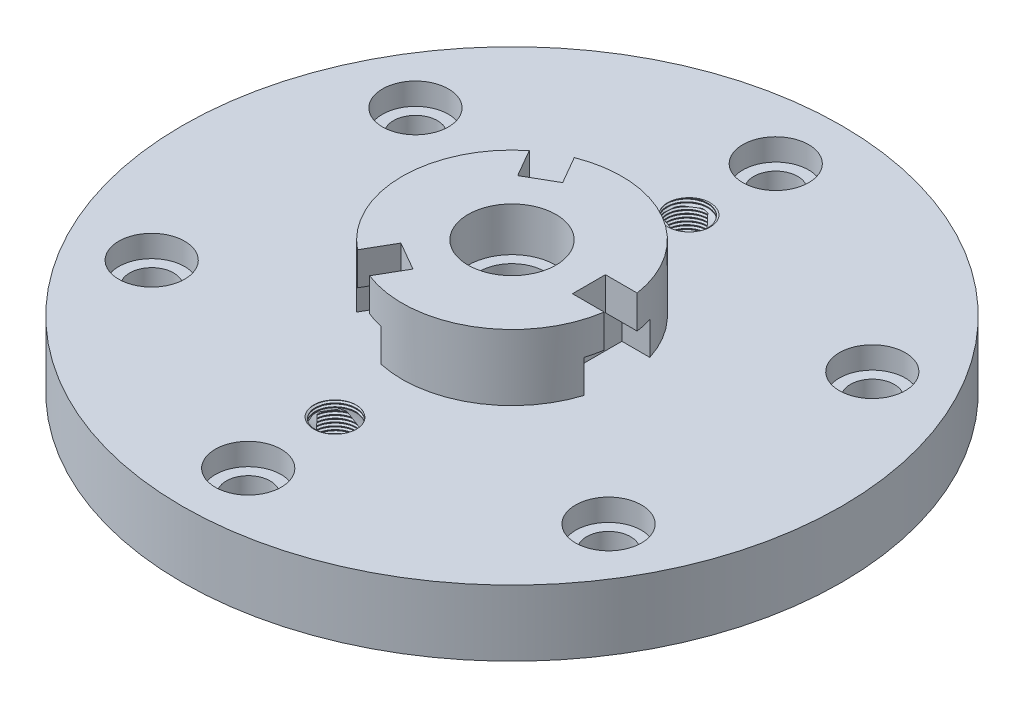
SolidWorks part; units mm, degrees
ref_plane "Front Plane" through (0, 0, 0) normal (0, 0, 1) x (1, 0, 0)
ref_plane "Top Plane" through (0, 0, 0) normal (0, 1, 0) x (1, 0, 0)
ref_plane "Right Plane" through (0, 0, 0) normal (1, 0, 0) x (0, 0, -1)
ref_axis "Z" through (0, 55, 0) along (0, -1, 0)
ref_axis "Y" through (0, 0, 165) along (0, 0, -1)
ref_axis "X" through (165, 0, 0) along (-1, 0, 0)
sketch "Sketch2" plane through (0, 0, 0) normal (0, 0, 1) x (1, 0, 0)
  line L0 (0, -58.6304) -> (0, 71.3696)
  line L1 (0, 55) -> (0, -55) construction
  line L2 (0, 71.3696) -> (-50, 71.3696)
  line L3 (-50, 71.3696) -> (-50, 41.3696)
  line L4 (-50, 41.3696) -> (-150, 41.3696)
  line L5 (-150, 41.3696) -> (-150, 11.3696)
  line L6 (-150, 11.3696) -> (-65, 11.3696)
  line L7 (-60, 6.3696) -> (-60, -3.6304)
  line L8 (-55, -8.6304) -> (-40, -8.6304)
  line L9 (-30, -18.6304) -> (-30, -58.6304)
  line L10 (-30, -58.6304) -> (0, -58.6304)
  arc A0 (-60, -3.6304) -> (-55, -8.6304) centre (-55, -3.6304) ccw
  arc A1 (-65, 11.3696) -> (-60, 6.3696) centre (-65, 6.3696) cw
  arc A2 (-40, -8.6304) -> (-30, -18.6304) centre (-40, -18.6304) cw
  point P15 (-60, -8.6304)
  point P18 (-60, 11.3696)
  point P21 (-30, -8.6304)
  dimension "D9" = 5
  dimension "D10" = 10
  dimension "D1" = 50
  dimension "D2" = 100
  dimension "D3" = 30
  dimension "D4" = 20
  dimension "D5" = 50
  dimension "D6" = 60
  dimension "D7" = 30
  dimension "D8" = 30
revolve "Revolve1" add sketch "Sketch2" angle 360 about axis through (0, 55, 0) along (0, -1, 0)
sketch "Sketch3" plane through (0, 0, 0) normal (0, 0, 1) x (1, 0, 0)
  line L0 (0, 71.3696) -> (-20, 71.3696)
  line L1 (50, 71.3696) -> (-50, 71.3696) construction
  line L2 (-20, 71.3696) -> (-20, 51.3696)
  line L4 (-20, 51.3696) -> (-15, 51.3696)
  line L5 (-15, 51.3696) -> (-15, -58.6304)
  line L6 (-30, -58.6304) -> (30, -58.6304) construction
  line L7 (-15, -58.6304) -> (0, -58.6304)
  line L8 (0, -58.6304) -> (0, 71.3696)
  dimension "D1" = 20
  dimension "D2" = 20
  dimension "D3" = 5
  dimension "D4" = 110
revolve "Cut-Revolve1" cut sketch "Sketch3" angle 360 about L8
sketch "Sketch6" plane through (0, 71.3696, 0) normal (0, 1, 0) x (1, 0, 0)
  line L0 (-11.0048, -34.0609) -> (-23.9952, -26.5609)
  line L1 (35, 7.5) -> (61.5171, 7.5)
  line L2 (35, 7.5) -> (35, -7.5)
  line L3 (35, -7.5) -> (61.5171, -7.5)
  line L4 (61.5171, 7.5) -> (61.5171, -7.5)
  line L5 (-11.0048, -34.0609) -> (-24.2634, -57.0254)
  line L6 (-24.2634, -57.0254) -> (-37.2537, -49.5254)
  line L7 (-23.9952, -26.5609) -> (-37.2537, -49.5254)
  line L8 (-23.9952, 26.5609) -> (-11.0048, 34.0609)
  line L9 (-23.9952, 26.5609) -> (-37.2537, 49.5254)
  line L10 (-37.2537, 49.5254) -> (-24.2634, 57.0254)
  line L11 (-11.0048, 34.0609) -> (-24.2634, 57.0254)
  point P16 (0, 0)
  dimension "D1" = 15
  dimension "D2" = 7.5
  dimension "D3" = 35
extrude "Cut-Extrude2" cut sketch "Sketch6" against normal blind 30
sketch "Sketch8" plane through (0, 41.3696, 0) normal (0, 1, 0) x (1, 0, 0)
  line L0 (-4.5096, -37.8109) -> (-30.4904, -22.8109)
  line L1 (35, 15) -> (65.7776, 15)
  line L2 (35, 15) -> (35, -15)
  line L3 (35, -15) -> (65.7776, -15)
  line L4 (65.7776, 15) -> (65.7776, -15)
  line L5 (-4.5096, -37.8109) -> (-19.8984, -64.4651)
  line L6 (-19.8984, -64.4651) -> (-45.8792, -49.4651)
  line L7 (-30.4904, -22.8109) -> (-45.8792, -49.4651)
  line L8 (-30.4904, 22.8109) -> (-4.5096, 37.8109)
  line L9 (-30.4904, 22.8109) -> (-45.8792, 49.4651)
  line L10 (-45.8792, 49.4651) -> (-19.8984, 64.4651)
  line L11 (-4.5096, 37.8109) -> (-19.8984, 64.4651)
  point P16 (0, 0)
  dimension "D1" = 30
  dimension "D2" = 35
  dimension "D3" = 15
extrude "Cut-Extrude3" cut sketch "Sketch8" along normal blind 15
sketch "Sketch9" plane through (0, 41.3696, 0) normal (0, 1, 0) x (1, 0, 0)
  circle A0 centre (0, 0) radius 120
  point P3 (0, 120)
  point P4 (0, -80)
  dimension "D1" = 240
  dimension "D2" = 80
hole_wizard "CBORE for M10 Hex Head Bolt1" positions "3DSketch1" profile "Sketch10" counterbore size "M10" standard "ANSI Metric" end condition through all
sketch3d "3DSketch1"
  point P0 (0, 41.3696, -120)
sketch "Sketch10" plane through (0, 41.3696, -120) normal (1, 0, 0) x (0, 0, 1)
  line L0 (0, 0) -> (0, 100)
  line L1 (0, 100) -> (10, 100)
  line L3 (10, 100) -> (10, 10)
  line L4 (10, 10) -> (15, 10)
  line L5 (15, 10) -> (15, 0)
  line L7 (15, 0) -> (0, 0)
  line L11 (0, -6.35) -> (0, 107.95) construction
  dimension "Thru Hole Dia." = 20
  dimension "Thru Hole Depth" = 100
  dimension "C'Bore Dia." = 30
  dimension "C'Bore Depth" = 10
pattern_circular "CirPattern1" count 6 every 60 about axis through (0, -58.6304, 0) along (0, -1, 0) of "CBORE for M10 Hex Head Bolt1"
hole_wizard "Tap Drill for M20x1.5 Tap2" positions "Sketch21" profile "Sketch22" hole size "M20x1.5" standard "ANSI Metric" end condition through all
sketch "Sketch21" plane through (0, 41.3696, 0) normal (0, 1, 0) x (1, 0, 0)
  point P0 (0, -80)
sketch "Sketch22" plane through (0, 41.3696, 80) normal (1, 0, 0) x (0, 0, 1)
  line L0 (0, 0) -> (0, 100)
  line L1 (0, 100) -> (9.25, 100)
  line L2 (9.25, 100) -> (9.25, 0)
  line L5 (9.25, 0) -> (0, 0)
  line L11 (0, -6.35) -> (0, 107.95) construction
  dimension "Thru Hole Dia." = 18.5
  dimension "Thru Hole Depth" = 100
thread "Thread1" pitch 1.5 method cut profile "Thread Profile2" start angle 0, offset 2, length 40, pitch 1.5, diameter 18.5
ref_plane "Plane2" through (-9.25, 43.3696, 80) normal (0, 0, 1) x (-1, 0, 0)
sketch "Thread Profile2" plane through (-9.25, 43.3696, 80) normal (0, 0, 1) x (-1, 0, 0)
  line L0 (0, 0) -> (0, 1.5) construction
  line L1 (0, 0) -> (0.8119, 0.4687)
  line L2 (0.8119, 0.4687) -> (0.8119, 0.6562)
  line L3 (0.8119, 0.6562) -> (0, 1.125)
  line L4 (0.8119, 0.5625) -> (0, 0.5625) construction
  line L11 (0, 0) -> (0, 1.125)
  point P2 (0, 0)
  dimension "Pitch" = 1.5
  dimension "Profile_Angle" = 60
  dimension "Profile_Land" = 0.1875
  dimension "Profile_Height" = 0.8119
pattern_circular "CirPattern2" count 2 every 180 about axis through (0, -58.6304, 0) along (0, -1, 0) of "Thread1"
pattern_circular "CirPattern3" count 2 every 180 about axis through (0, -58.6304, 0) along (0, -1, 0) of "Tap Drill for M20x1.5 Tap2"
ref_plane "Plane3" through (30, 0, 0) normal (1, 0, 0) x (0, 0, -1)
sketch "Sketch29" plane through (30, 0, 0) normal (1, 0, 0) x (0, 0, -1)
  line L0 (0, -28.6304) -> (0, -80.8611) construction
  line L1 (8, -28.6304) -> (8, -80.8611)
  line L2 (-8, -28.6304) -> (-8, -80.8611)
  line L3 (-30, -58.6304) -> (30, -58.6304) construction
  arc A0 (8, -28.6304) -> (-8, -28.6304) centre (0, -28.6304) ccw
  arc A1 (-8, -80.8611) -> (8, -80.8611) centre (0, -80.8611) ccw
  point P3 (0, -54.7457)
  dimension "D1" = 30
  dimension "D2" = 16
extrude "Cut-Extrude5" cut sketch "Sketch29" against normal blind 5
pattern_circular "CirPattern4" count 2 every 180 about axis through (0, -58.6304, 0) along (0, -1, 0) of "Cut-Extrude5"
